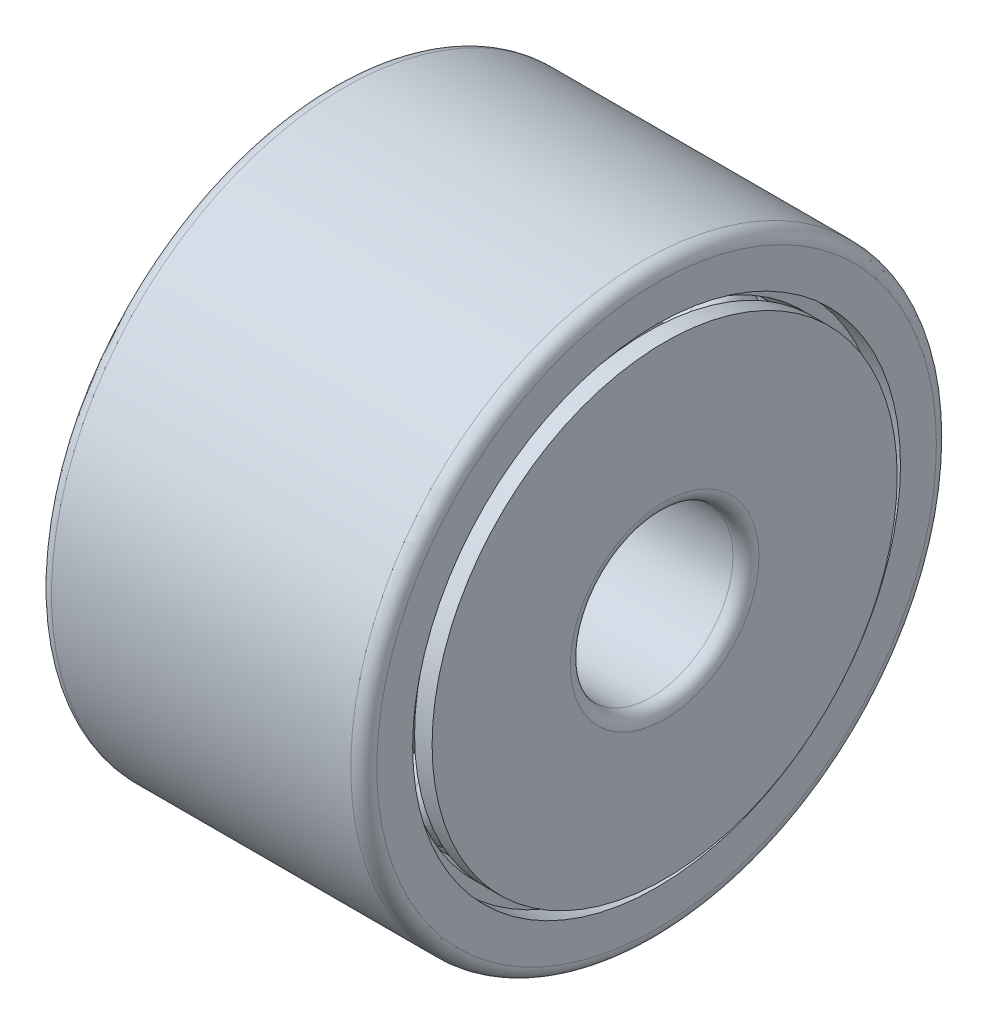
SolidWorks part; units mm, degrees
ref_plane "Plane1" through (0, 0, 0) normal (0, 0, 1) x (1, 0, 0)
ref_plane "Plane2" through (0, 0, 0) normal (0, 1, 0) x (1, 0, 0)
ref_plane "Plane3" through (0, 0, 0) normal (1, 0, 0) x (0, 0, -1)
sketch "Clipboard" plane through (0, 0, 0) normal (0, 0, 1) x (1, 0, 0)
  line L0 (-10, 0) -> (10, 0) construction
  line L1 (0, 0) -> (27.0344, -5.7463)
  line L2 (0, 0) -> (22.4793, 28.7722)
  line L3 (0, 0) -> (27.9428, -35.7651)
  line L4 (0, 0) -> (-22.3471, -0.7804)
  dimension "Race_OD" = 45.3866
  dimension "Race_ID" = 27.6384
sketch "OutRacSke" plane through (0, 0, 0) normal (0, 0, 1) x (1, 0, 0)
  line L0 (-14.0229, 22.6933) -> (-14.0229, 23.8026)
  line L1 (-14.0229, 23.8026) -> (-15.875, 23.8026)
  line L2 (-15.875, 23.8026) -> (-15.875, 27.305)
  line L3 (-14.605, 28.575) -> (14.605, 28.575)
  line L4 (15.875, 27.305) -> (15.875, 23.8026)
  line L5 (15.875, 23.8026) -> (14.0229, 23.8026)
  line L6 (14.0229, 23.8026) -> (14.0229, 22.6933)
  line L7 (14.0229, 22.6933) -> (-14.0229, 22.6933)
  line L8 (-7.9375, 0) -> (7.9375, 0) construction
  arc A0 (-15.875, 27.305) -> (-14.605, 28.575) centre (-14.605, 27.305) cw
  arc A1 (14.605, 28.575) -> (15.875, 27.305) centre (14.605, 27.305) cw
  dimension "D1" = 14.0229
  dimension "Race_OD" = 45.3866
  dimension "Cyl_Len" = 28.0458
revolve "OuterRace" add sketch "OutRacSke" angle 360 about L8 reverse direction yes
sketch "RolDetSke" plane through (0, 0, 0) normal (0, 0, 1) x (1, 0, 0)
  line L0 (-14.0229, 20.9261) -> (-14.0229, 18.2562)
  line L1 (-14.0229, 18.2562) -> (14.0229, 18.2562)
  line L2 (14.0229, 18.2562) -> (14.0229, 20.9261)
  line L3 (12.243, 22.706) -> (-12.243, 22.706)
  line L4 (-28.575, 18.2562) -> (28.575, 18.2562) construction
  arc A0 (14.0229, 20.9261) -> (12.243, 22.706) centre (12.243, 20.9261) ccw
  arc A1 (-12.243, 22.706) -> (-14.0229, 20.9261) centre (-12.243, 20.9261) ccw
  dimension "Cyl_Len" = 28.0458
  dimension "radius" = 1.7799
  dimension "Roller_diameter" = 8.8995
revolve "RollerDetailed" add sketch "RolDetSke" angle 360 about L4 reverse direction yes
ref_axis "Axis1" through (-50, 0, 0) along (1, 0, 0)
pattern_circular "RollersDetailed" count 12 every 30 about axis through (-50, 0, 0) along (1, 0, 0) of "RollerDetailed"
sketch "RolSimSke" plane through (0, 25.4, 0) normal (0, 0, 1) x (1, 0, 0)
  line L0 (-14.0229, -4.4612) -> (-14.0229, -9.8009)
  line L1 (-25.4, -25.4) -> (25.4, -25.4) construction
  line L2 (14.0229, -9.8009) -> (14.0229, -4.4612)
  line L3 (12.243, -2.6813) -> (-12.243, -2.6813)
  line L5 (12.243, -11.5808) -> (-12.243, -11.5808)
  arc A0 (14.0229, -4.4612) -> (12.243, -2.6813) centre (12.243, -4.4612) ccw
  arc A1 (-12.243, -2.6813) -> (-14.0229, -4.4612) centre (-12.243, -4.4612) ccw
  arc A2 (14.0229, -9.8009) -> (12.243, -11.5808) centre (12.243, -9.8009) cw
  arc A3 (-12.243, -11.5808) -> (-14.0229, -9.8009) centre (-12.243, -9.8009) cw
  dimension "radius" = 1.7799
  dimension "Roller_diameter" = 8.8995
  dimension "Cyl_Len" = 28.0458
revolve "RollersSimplified" [suppressed] add sketch "RolSimSke" angle 360 about L1
sketch "InsRacSke" plane through (0, 0, 0) normal (0, 0, 1) x (1, 0, 0)
  line L0 (-14.949, 13.8192) -> (-14.949, 22.6933)
  line L1 (-14.949, 22.6933) -> (-16.6624, 22.6933)
  line L2 (-16.6624, 22.6933) -> (-16.6624, 9.2075)
  line L3 (-15.3924, 7.9375) -> (-0.84, 7.9375)
  line L4 (0.84, 7.9375) -> (15.3924, 7.9375)
  line L5 (16.6624, 9.2075) -> (16.6624, 22.6933)
  line L6 (16.6624, 22.6933) -> (14.949, 22.6933)
  line L7 (14.949, 22.6933) -> (14.949, 13.8192)
  line L8 (14.949, 13.8192) -> (-14.949, 13.8192)
  line L9 (-7.9375, 0) -> (7.9375, 0) construction
  arc A0 (-16.6624, 9.2075) -> (-15.3924, 7.9375) centre (-15.3924, 9.2075) ccw
  arc A1 (-0.84, 7.9375) -> (0.84, 7.9375) centre (0, 6.985) cw
  arc A2 (15.3924, 7.9375) -> (16.6624, 9.2075) centre (15.3924, 9.2075) ccw
  dimension "radius" = 1.27
  dimension "Bore" = 15.875
  dimension "halfWidth" = 16.6624
  dimension "Race_OD" = 45.3866
  dimension "Race_ID" = 27.6384
  dimension "SlotWidth" = 29.8979
revolve "InnerRace" add sketch "InsRacSke" angle 360 about L9 reverse direction yes
equation "\"halfWidth@OutRacSke\" =  \"Width@OutRacSke\" / 2"
equation "\"CLdia@Clipboard\" =  ( \"Race_OD@Clipboard\" + \"Race_ID@Clipboard\" )  / 2"
equation "\"CLRad@RolDetSke\" = ( \"Race_OD@Clipboard\" + \"Race_ID@Clipboard\" )  / 4"
equation "\"Roller_diameter@RolDetSke\" =  ( \"Race_OD@Clipboard\" -  \"Race_ID@Clipboard\" )  / 2 + .001"
equation "\"Roller_diameter@RolSimSke\" = ( \"Race_OD@Clipboard\" -  \"Race_ID@Clipboard\" )  / 2 + .001"
equation "\"radius@RolDetSke\" = \"Roller_diameter@RolDetSke\" / 5"
equation "\"radius@RolSimSke\" = \"Roller_diameter@RolSimSke\" / 5"
equation "\"Cyl_Len@OutRacSke\" = \"Cyl_Len@RolDetSke\""
equation "\"Cyl_Len@RolSimSke\" = \"Cyl_Len@RolDetSke\""
equation "\"halfCylLen@RolDetSke\" = \"Cyl_Len@RolDetSke\" / 2"
equation "\"offset@InsRacSke\" = \"radius@InsRacSke\" * 0.75"
equation "\"SlotWidth@InsRacSke\" =  ( \"Width@OutRacSke\" + \"Cyl_Len@RolDetSke\" )  / 2"
equation "\"halfSlotWidth@InsRacSke\" = \"SlotWidth@InsRacSke\" / 2"
equation "\"D1@OutRacSke\" = \"Cyl_Len@OutRacSke\" / 2"
equation "\"Max_count@Clipboard\" = int( 3.14159265 / atn(( \"Roller_diameter@RolDetSke\" / 2) / sqr( \"CLRad@RolDetSke\"  *  \"CLRad@RolDetSke\" - ( \"Roller_diameter@RolDetSke\" / 2) *  ( \"Roller_diameter@RolDetSke\" / 2))))"
equation "\"Max_count@Clipboard\" = ((sgn( \"Max_count@Clipboard\" - \"Count@Clipboard\" )-1)*( \"Max_count@Clipboard\" - \"Count@Clipboard\" ))/-2+ \"Count@Clipboard\""
equation "\"Count@RollersDetailed\" = int( \"Show_count@Clipboard\" ) "
equation "\"Count@RollersDetailed\" = ((sgn( \"Count@RollersDetailed\" - \"Max_count@Clipboard\" )-1)*( \"Count@RollersDetailed\" - \"Max_count@Clipboard\" ))/-2+ \"Max_count@Clipboard\""
equation "\"Count@RollersDetailed\" = ((sgn( \"Count@RollersDetailed\" - \"Min_count@Clipboard\" )+1)*( \"Count@RollersDetailed\" - \"Min_count@Clipboard\"))/2 +\"Min_count@Clipboard\""
equation "\"Angle@RollersDetailed\" = 360.0 / \"Max_count@Clipboard\""
equation "\"Bore@RolSimSke\" = \"Race_ID@Clipboard\""
equation "\"Race_ID@InsRacSke\" = \"Race_ID@Clipboard\""
equation "\"Race_OD@InsRacSke\" = \"Race_OD@Clipboard\""
equation "\"halfWidth@InsRacSke\" = \"Width_IR@InsRacSke\" / 2"
equation "\"halfLength@RolSimSke\" = \"Cyl_Len@RolSimSke\" / 2"
equation "\"Race_OD@OutRacSke\" = \"Race_OD@Clipboard\""
